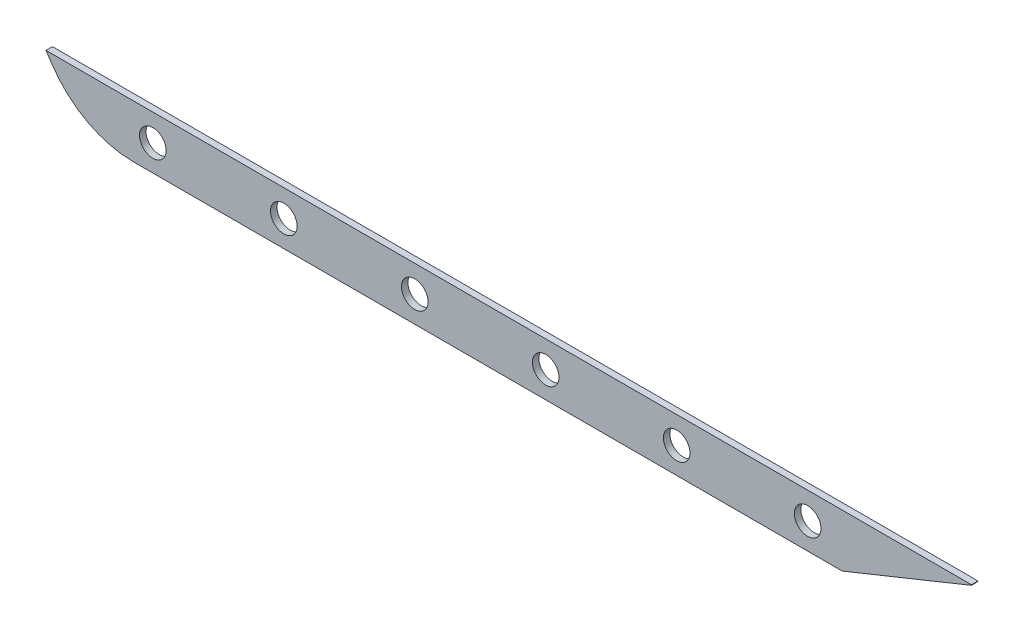
SolidWorks part; units mm, degrees
material "5052-H34"
ref_plane "Front Plane" through (0, 0, 0) normal (0, 0, 1) x (1, 0, 0)
ref_plane "Top Plane" through (0, 0, 0) normal (0, 1, 0) x (1, 0, 0)
ref_plane "Right Plane" through (0, 0, 0) normal (1, 0, 0) x (0, 0, -1)
sketch "Sketch1" plane through (0, 0, 0) normal (0, 0, 1) x (1, 0, 0)
  line L3 (428.1206, 28.9396) -> (0.5404, 28.9396)
  line L6 (-98.8794, 3.851) -> (-31.8794, -96.649)
  line L7 (428.1206, 28.9396) -> (403.1206, -71.149)
  line L9 (403.1206, -71.149) -> (366, -96.649)
  line L10 (-31.8794, -96.649) -> (366, -96.649)
  line L11 (0.5404, 28.9396) -> (-115.6052, 28.9396)
  line L12 (-98.8794, 3.851) -> (-115.6052, 28.9396)
  line L13 (-49.0861, -70.839) -> (403.198, -70.839)
  circle A0 centre (3.1206, -83.899) radius 6.5
  circle A1 centre (67.1206, -83.899) radius 6.5
  circle A2 centre (131.1206, -83.899) radius 6.5
  circle A3 centre (195.1206, -83.899) radius 6.5
  circle A4 centre (259.1206, -83.899) radius 6.5
  circle A5 centre (323.1206, -83.899) radius 6.5
  point P0 (-48.8794, -71.149)
  point P2 (-31.8794, -96.649)
  point P8 (48, -83.899)
  point P9 (403.1206, -71.149)
  point P23 (-49.0861, -70.839)
  point P25 (403.198, -70.839)
  dimension "D2" = 64
  dimension "D4" = 64
  dimension "D1" = 25.5
  dimension "D3" = 75
  dimension "D5" = 25
  dimension "D6" = 80
  dimension "D7" = 527
  dimension "D8" = 180
  dimension "D9" = 64
  dimension "D10" = 64
  dimension "D11" = 64
  dimension "D12" = 123.69
  dimension "D13" = 12.75
  dimension "D14" = 25.81
  dimension "D15" = 25.81
extrude "Boss-Extrude1" add sketch "Sketch1" along normal blind 3.175 contours L3 L11 L12 L6 L10 L9 L7
extrude "Cut-Extrude1" cut sketch "Sketch1<4>" along normal through all contours A0 | A1 | A2 | A3 | A4 | A5 region at (3.1206, -83.899, 0)
sketch "Sketch1<4>" plane through (0, 0, 0) normal (0, 0, 1) x (1, 0, 0) same geometry as "Sketch1"
sketch "Sketch2" plane through (0, 0, 0) normal (0, 0, -1) x (-1, 0, 0)
  circle A0 centre (-291.1206, -83.899) radius 6.5
  circle A2 centre (-241.5603, -124.3932) radius 6.5
  circle A3 centre (-192, -83.899) radius 6.5
  circle A4 centre (-128, -83.899) radius 6.5
  circle A5 centre (-64, -83.899) radius 6.5
  circle A6 centre (0, -83.899) radius 6.5
  dimension "D2" = 0
  dimension "D3" = 64
  dimension "D4" = 64
  dimension "D5" = 64
  dimension "D6" = 64
  dimension "D7" = 64
  dimension "D1" = 32
sketch "Sketch5" plane through (0, 0, 0) normal (0, 0, -1) x (-1, 0, 0)
  line L0 (48.8794, -71.149) -> (-14.2353, -96.649)
  line L1 (31.8794, -96.649) -> (-366, -96.649) construction
  line L2 (-14.2353, -96.649) -> (31.8794, -96.649)
  line L3 (31.8794, -96.649) -> (48.8794, -71.149)
  line L6 (-366, -96.649) -> (-403.1206, -71.149)
  line L7 (-403.1206, -71.149) -> (-352, -71.149)
  line L9 (-352, -71.149) -> (-326.5, -96.649)
  line L11 (-366, -96.649) -> (-326.5, -96.649)
  dimension "D1" = 22
  dimension "D2" = 45
extrude "Cut-Extrude2" [suppressed] cut sketch "Sketch5" against normal up to next
sketch "Sketch6" plane through (0, 0, 3.175) normal (0, 0, 1) x (1, 0, 0)
  line L0 (-48.8794, -71.149) -> (14.2353, -96.649)
  line L1 (-31.8794, -96.649) -> (366, -96.649) construction
  line L2 (14.2353, -96.649) -> (-31.8794, -96.649)
  line L3 (-31.8794, -96.649) -> (-48.8794, -71.149)
  dimension "D1" = 158
fillet "Fillet1" radius 48 1 edges at (-31.8794, -96.649, 1.5875)
sketch "Sketch7" plane through (0, 0, 3.175) normal (0, 0, 1) x (1, 0, 0)
  line L0 (403.1206, -71.149) -> (340.0059, -96.649)
  line L1 (-31.8794, -96.649) -> (366, -96.649) construction
  line L2 (340.0059, -96.649) -> (366, -96.649)
  line L3 (366, -96.649) -> (403.1206, -71.149)
  dimension "D1" = 22
extrude "Cut-Extrude3" cut sketch "Sketch7" against normal blind 10
sketch "Sketch9" plane through (0, 0, 0) normal (0, 0, -1) x (-1, 0, 0)
  line L0 (-403.1206, -71.149) -> (48.8794, -71.149)
  line L1 (48.8794, -71.149) -> (48.8794, -114.9143)
  line L2 (48.8794, -114.9143) -> (-403.1206, -114.9143)
  line L3 (-403.1206, -114.9143) -> (-403.1206, -71.149)
extrude "Cut-Extrude4" [suppressed] cut sketch "Sketch9" against normal blind 10
sketch "Sketch11" plane through (0, 0, 3.175) normal (0, 0, 1) x (1, 0, 0)
  line L0 (-49.0861, -70.839) -> (403.198, -70.839) construction
  line L1 (-49.0861, -70.839) -> (403.198, -70.839)
  line L3 (-115.6052, 28.9396) -> (428.1206, 28.9396)
  line L4 (428.1206, 28.9396) -> (403.198, -70.839)
  line L5 (-49.0861, -70.839) -> (-115.6052, 28.9396)
extrude "Cut-Extrude5" cut sketch "Sketch11" against normal blind 10
